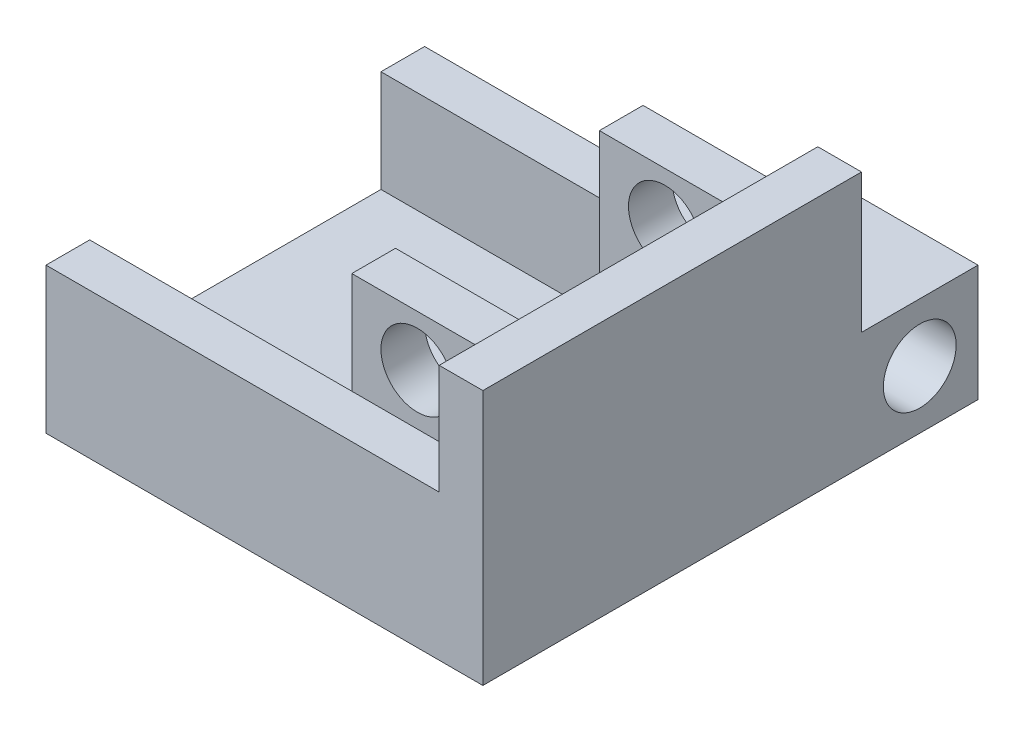
SolidWorks part; units mm, degrees
ref_plane "Front Plane" through (0, 0, 0) normal (0, 0, 1) x (1, 0, 0)
ref_plane "Top Plane" through (0, 0, 0) normal (0, 1, 0) x (1, 0, 0)
ref_plane "Right Plane" through (0, 0, 0) normal (1, 0, 0) x (0, 0, -1)
sketch "Sketch1" plane through (0, 0, 0) normal (0, 1, 0) x (1, 0, 0)
  line L0 (13.5, 10) -> (13.5, 13)
  line L1 (-13.5, -10) -> (13.5, -10)
  line L2 (-13.5, -10) -> (-13.5, 10)
  line L3 (-13.5, 10) -> (13.5, 10)
  line L4 (13.5, -10) -> (13.5, 10)
  line L5 (-13.5, -10) -> (13.5, 10) construction
  line L6 (-13.5, 10) -> (13.5, -10) construction
  line L11 (13.5, 13) -> (4.5, 13)
  line L12 (4.5, 13) -> (4.5, 10)
  line L13 (13.5, -10) -> (13.5, -13)
  line L14 (13.5, -13) -> (4.5, -13)
  line L15 (4.5, -13) -> (4.5, -10)
  line L16 (13.5, 13) -> (16.5, 13)
  line L17 (16.5, 13) -> (16.5, -13)
  line L18 (16.5, -13) -> (13.5, -13)
  line L19 (4.5, -13) -> (-13.5, -13)
  line L20 (-13.5, -13) -> (-13.5, -10)
  line L21 (4.5, 13) -> (-13.5, 13)
  line L22 (-13.5, 13) -> (-13.5, 10)
  point P0 (0, 0)
  point P6 (0, 0)
  dimension "D1" = 27
  dimension "D2" = 20
  dimension "D3" = 3
  dimension "D4" = 9
  dimension "D5" = 3
extrude "Boss-Extrude1" add sketch "Sketch1" along normal blind 3 contours L1 L4 L3 L2 | L11 L12 L3 L0 | L15 L14 L13 L1
extrude "Boss-Extrude2" add sketch "Sketch1<4>" along normal blind 4 from surface contours L15 L14 L13 L1 | L11 L12 L3 L0 region at (9, 0, -11.5) region at (9, 0, 11.5) starting at face at (2.25, 3, 0)
sketch "Sketch1<4>" plane through (0, 0, 0) normal (0, 1, 0) x (1, 0, 0) same geometry as "Sketch1"
sketch "Sketch2" plane through (0, 7, 0) normal (0, 1, 0) x (1, 0, 0)
  line L0 (13.5, -10) -> (13.5, 10) construction
  line L1 (4.5, -13) -> (13.5, -13)
  line L2 (4.5, -13) -> (4.5, -7)
  line L3 (4.5, -7) -> (13.5, -7)
  line L4 (13.5, -13) -> (13.5, -7)
  line L6 (4.5, 13) -> (13.5, 13)
  line L7 (4.5, 13) -> (4.5, 7)
  line L8 (4.5, 7) -> (13.5, 7)
  line L9 (13.5, 13) -> (13.5, 7)
  dimension "D1" = 6
extrude "Boss-Extrude3" add sketch "Sketch2" along normal blind 3
extrude "Boss-Extrude4" add sketch "Sketch2<2>" along normal blind 2 from surface starting at face at (1.5, 3, 0)
sketch "Sketch2<2>" plane through (0, 7, 0) normal (0, 1, 0) x (1, 0, 0) same geometry as "Sketch2"
extrude "Boss-Extrude5" add sketch "Sketch1<5>" along normal up to surface (10 mm away) contours L18 L17 L16 L0 L4 L13 | L20 L19 L15 L1 | L21 L22 L3 L12 region at (15, 0, 0) region at (-4.5, 0, -11.5) region at (-4.5, 0, 11.5) up to face at (9, 10, -10)
sketch "Sketch1<5>" plane through (0, 0, 0) normal (0, 1, 0) x (1, 0, 0) same geometry as "Sketch1"
sketch "Sketch3" plane through (0, 10, 0) normal (0, 1, 0) x (1, 0, 0)
  line L0 (-13.5, -13) -> (16.5, -13) construction
  line L1 (16.5, 13) -> (13.5, 13)
  line L2 (16.5, 13) -> (16.5, -13)
  line L3 (16.5, -13) -> (13.5, -13)
  line L4 (13.5, 13) -> (13.5, -13)
  line L5 (13.5, -7) -> (13.5, 7) construction
extrude "Boss-Extrude6" add sketch "Sketch3" along normal blind 7.54
sketch "Sketch4" plane through (0, 10, 0) normal (0, 1, 0) x (1, 0, 0)
  line L0 (13.5, -7) -> (13.5, -13) construction
  line L1 (4.5, 10) -> (13.5, 10)
  line L2 (4.5, 10) -> (4.5, 7)
  line L3 (4.5, 7) -> (13.5, 7)
  line L4 (13.5, 10) -> (13.5, 7)
  line L5 (4.5, -7) -> (13.5, -7)
  line L6 (4.5, -7) -> (4.5, -10)
  line L7 (4.5, -10) -> (13.5, -10)
  line L8 (13.5, -7) -> (13.5, -10)
extrude "Boss-Extrude7" add sketch "Sketch4" along normal blind 7
sketch "Sketch5" plane through (0, 0, 10) normal (0, 0, 1) x (1, 0, 0)
  line L0 (9, 17) -> (9, 13.5) construction
  line L1 (4.5, 17) -> (13.5, 17) construction
  line L5 (4.5, 17) -> (4.5, 10) construction
  line L6 (13.5, 17.54) -> (13.5, 10) construction
  line L7 (4.5, 13.5) -> (13.5, 13.5) construction
  circle A0 centre (9, 13.5) radius 2.5
  point P9 (0, 0)
  dimension "D1" = 5
extrude "Cut-Extrude1" cut sketch "Sketch5" against normal through all both and the other way through all
sketch "Sketch6" plane through (16.5, 0, 0) normal (1, 0, 0) x (0, 0, -1)
  line L0 (13, 8) -> (21, 0) construction
  line L1 (13, 0) -> (21, 0)
  line L2 (13, 0) -> (13, 8)
  line L3 (13, 8) -> (21, 8)
  line L4 (21, 0) -> (21, 8)
  circle A0 centre (17, 4) radius 2.5
  point P7 (17, 4)
  dimension "D3" = 5
  dimension "D1" = 8
  dimension "D2" = 8
extrude "Boss-Extrude8" add sketch "Sketch6" against normal blind 10
